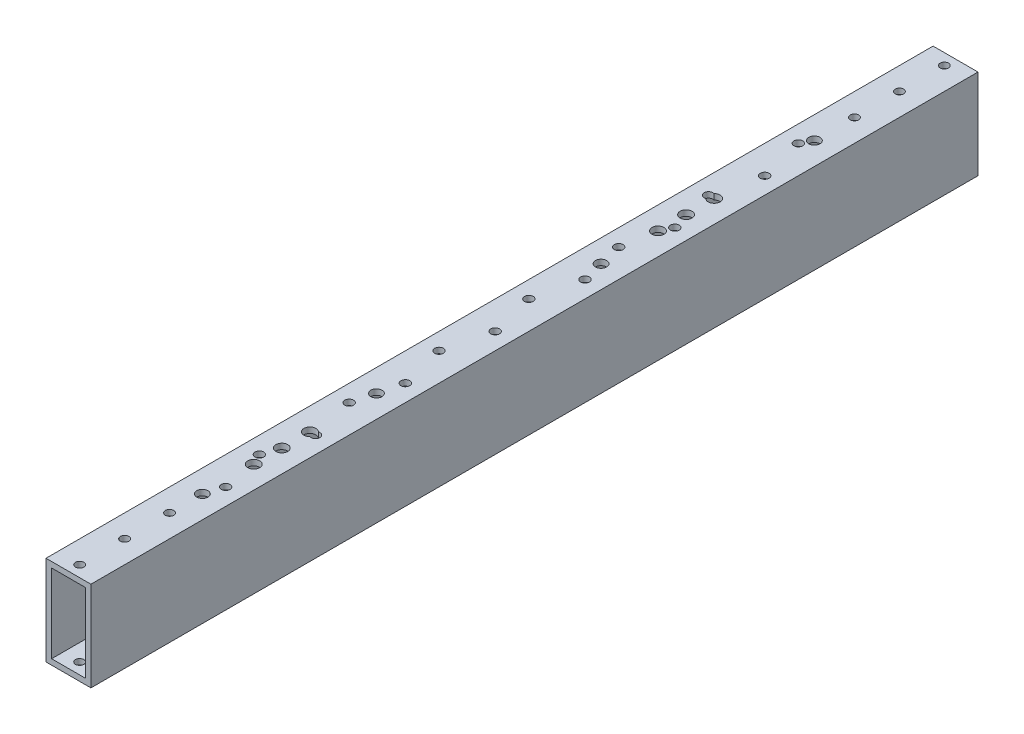
SolidWorks part; units mm, degrees
material "6061-T6 (SS)"
ref_plane "Front Plane" through (0, 0, 0) normal (0, 0, 1) x (1, 0, 0)
ref_plane "Top Plane" through (0, 0, 0) normal (0, 1, 0) x (1, 0, 0)
ref_plane "Right Plane" through (0, 0, 0) normal (1, 0, 0) x (0, 0, -1)
sketch "Sketch1" plane through (0, 0, 0) normal (0, 0, 1) x (1, 0, 0)
  line L1 (-12.7, -25.4) -> (12.7, -25.4)
  line L2 (-12.7, -25.4) -> (-12.7, 25.4)
  line L3 (-12.7, 25.4) -> (12.7, 25.4)
  line L4 (12.7, -25.4) -> (12.7, 25.4)
  line L5 (-12.7, -25.4) -> (12.7, 25.4) construction
  line L6 (-12.7, 25.4) -> (12.7, -25.4) construction
  point P0 (0, 0)
  point P5 (0, 0)
  point P8 (0, 0)
  point P9 (0, 0)
  point P11 (0, 0)
  dimension "D1" = 50.8
  dimension "D2" = 25.4
extrude "Extrude-Thin1" add sketch "Sketch1" along normal blind 501.65 thin thin type one direction reverse wall 3.175
hole_wizard "3/16 (0.1875) Diameter Hole1" positions "3DSketch1" profile "Sketch3" hole size "3/16" standard "ANSI Inch" end condition through all
sketch3d "3DSketch1"
  line L1 (12.7, 25.4, 0) -> (-12.7, 25.4, 0) construction
  line L6 (0, 25.4, 501.65) -> (0, 25.4, 0) construction
  line L7 (12.7, 25.4, 501.65) -> (-12.7, 25.4, 501.65) construction
  point P57 (0, 25.4, 6.35)
  point P59 (0, 25.4, 31.75)
  point P61 (0, 25.4, 57.15)
  point P63 (0, 25.4, 469.9)
  point P65 (0, 25.4, 444.5)
  point P67 (0, 25.4, 495.3)
  dimension "D1" = 25.4
  dimension "D2" = 25.4
  dimension "D3" = 6.35
  dimension "D4" = 25.4
  dimension "D5" = 25.4
  dimension "D6" = 6.35
sketch "Sketch3" plane through (0, 25.4, 495.3) normal (1, 0, 0) x (0, 0, 1)
  line L0 (0, 0) -> (0, 50.8)
  line L1 (0, 50.8) -> (2.3812, 50.8)
  line L2 (2.3812, 50.8) -> (2.3812, 0)
  line L5 (2.3812, 0) -> (0, 0)
  line L11 (0, -6.35) -> (0, 107.95) construction
  dimension "Thru Hole Dia." = 4.7625
  dimension "Thru Hole Depth" = 50.8
hole_wizard "1/4 (0.25) Diameter Hole1" positions "Sketch7" profile "Sketch6" hole size "1/4" standard "ANSI Inch"
sketch "Sketch7" plane through (0, 25.4, 0) normal (0, 1, 0) x (1, 0, 0)
  point P6 (0, -79.831)
  point P9 (0, -425.9339)
  point P23 (0, -327.499)
  point P26 (0, -200.481)
sketch "Sketch6" plane through (0, 25.4, 79.831) normal (1, 0, 0) x (0, 0, 1)
  line L0 (0, 0) -> (0, 27.3077)
  line L1 (0, 27.3077) -> (3.175, 25.4)
  line L2 (3.175, 25.4) -> (3.175, 0)
  line L5 (3.175, 0) -> (0, 0)
  line L10 (0, 27.3077) -> (-3.175, 25.4) construction
  line L11 (0, -6.35) -> (0, 107.95) construction
  dimension "Hole Dia." = 6.35
  dimension "Hole Depth" = 25.4
  dimension "Drill Angle" = 118
hole_wizard "1/4 Clearance Hole1" positions "Sketch8" profile "Sketch9" hole size "1/4" standard "ANSI Inch"
sketch "Sketch8" plane through (381, 25.4, 250.825) normal (0, 1, 0) x (1, 0, 0)
  point P0 (381, 82.55)
  point P3 (381, 98.425)
  point P6 (381, 114.3)
  point P9 (381, -146.05)
  point P12 (381, -130.175)
  point P15 (381, -114.3)
  point P18 (-381, -146.05)
  point P21 (-381, -130.175)
  point P24 (-381, -114.3)
  point P27 (-381, 82.55)
  point P30 (-381, 98.425)
  point P33 (-381, 114.3)
sketch "Sketch9" plane through (762, 25.4, 168.275) normal (1, 0, 0) x (0, 0, 1)
  line L0 (0, 0) -> (0, 40.1298)
  line L1 (0, 40.1298) -> (3.3782, 38.1)
  line L2 (3.3782, 38.1) -> (3.3782, 0)
  line L3 (3.3782, 0) -> (0, 0)
  line L4 (0, 40.1298) -> (-3.3782, 38.1) construction
  line L5 (0, -6.35) -> (0, 107.95) construction
  dimension "Hole Dia." = 6.7564
  dimension "Hole Depth" = 38.1
  dimension "Drill Angle" = 118
hole_wizard "3/16 (0.195) Diameter Hole1" positions "Sketch10" profile "Sketch11" hole size "3/16" standard "ANSI Inch" end condition through all
sketch "Sketch10" plane through (0, -25.4, 0) normal (0, -1, 0) x (-1, 0, 0)
  point P0 (3.1693, -85.725)
  point P3 (-3.1807, -111.125)
  point P6 (3.1693, -136.525)
  point P9 (-3.1807, -161.925)
  point P12 (3.1693, -187.325)
  point P15 (-3.1807, -212.725)
  point P18 (3.1693, -238.125)
  point P21 (-3.1807, -263.525)
  point P24 (3.1693, -288.925)
  point P27 (-3.1807, -314.325)
  point P30 (3.1693, -339.725)
  point P33 (-3.1807, -365.125)
  point P36 (3.1693, -390.525)
  point P39 (-3.1807, -415.925)
sketch "Sketch11" plane through (-3.1693, -25.4, 85.725) normal (1, 0, 0) x (0, 0, -1)
  line L0 (0, 0) -> (0, 50.8)
  line L1 (0, 50.8) -> (2.4765, 50.8)
  line L2 (2.4765, 50.8) -> (2.4765, 0)
  line L5 (2.4765, 0) -> (0, 0)
  line L11 (0, -6.35) -> (0, 107.95) construction
  dimension "Thru Hole Dia." = 4.953
  dimension "Thru Hole Depth" = 50.8
